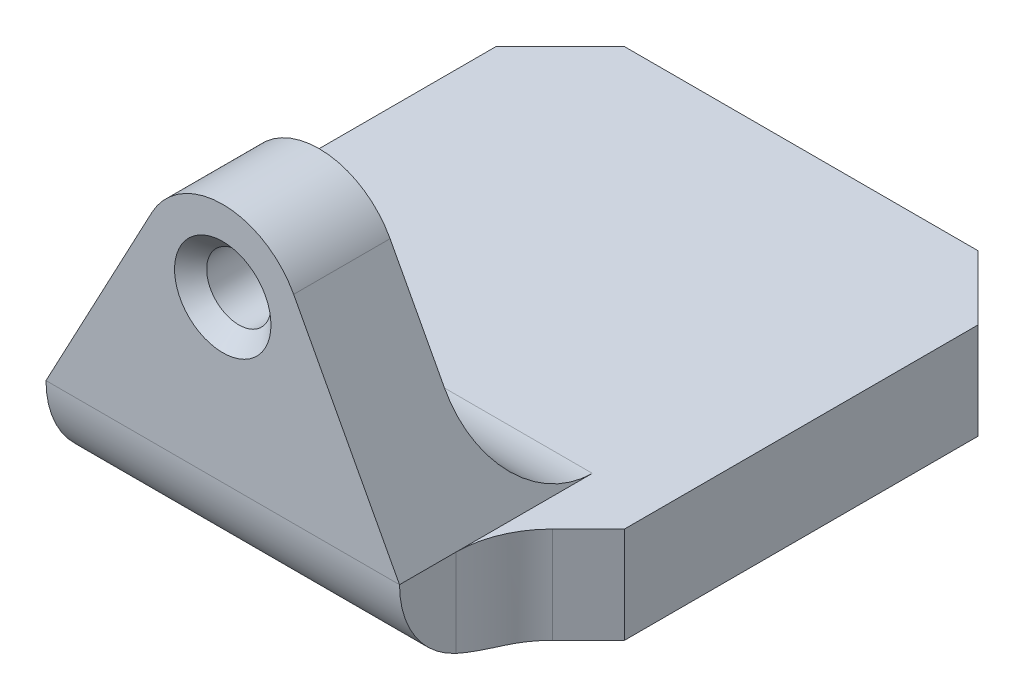
SolidWorks part; units mm, degrees
material "PE 高密度"
ref_plane "前视基准面" through (0, 0, 0) normal (0, 0, 1) x (1, 0, 0)
ref_plane "上视基准面" through (0, 0, 0) normal (0, 1, 0) x (1, 0, 0)
ref_plane "右视基准面" through (0, 0, 0) normal (1, 0, 0) x (0, 0, -1)
other "Configuration Table"
sketch "草图1" plane through (0, 0, 0) normal (0, 1, 0) x (1, 0, 0)
  line L1 (-15, 15) -> (15, 15)
  line L2 (-15, 15) -> (-15, -15)
  line L3 (-15, -15) -> (15, -15)
  line L4 (15, 15) -> (15, -15)
  line L5 (-15, 15) -> (15, -15) construction
  line L6 (-15, -15) -> (15, 15) construction
  point P0 (0, 0)
  dimension "D1" = 30
  dimension "D2" = 30
extrude "凸台-拉伸1" add sketch "草图1" along normal blind 6
chamfer "倒角1" distance 4 angle 45 4 edges at (-15, 3, -15) (15, 3, -15) (15, 3, 15) (-15, 3, 15)
sketch "草图2" plane through (0, 0, 15) normal (0, 0, 1) x (1, 0, 0)
  line L0 (0, 0) -> (0, 22.777) construction
  line L1 (-11, 6) -> (-4.4118, 18.3529)
  line L2 (11, 6) -> (4.4118, 18.3529)
  line L4 (-11, 0) -> (11, 0)
  line L5 (11, 0) -> (11, 6)
  line L6 (11, 6) -> (-11, 6)
  line L7 (-11, 6) -> (-11, 0)
  line L8 (-11, 0) -> (11, 0)
  line L9 (11, 0) -> (11, 6)
  line L11 (-11, 6) -> (-11, 0)
  circle A0 centre (0, 16) radius 2
  arc A1 (4.4118, 18.3529) -> (-4.4118, 18.3529) centre (0, 16) ccw
  dimension "D3" = 4
  dimension "D4" = 10
  dimension "D2" = 14
  dimension "D1" = 0
extrude "凸台-拉伸2" add sketch "草图2" along normal blind 6
fillet "圆角1" radius 6 1 edges at (0, 0, 21)
fillet "圆角2" radius 6 2 edges at (-11, 3, 15) (11, 3, 15)
fillet "圆角3" radius 6 1 edges at (0, 6, 15)
chamfer "倒角2" distance 1 angle 45 2 edges at (2, 16, 15) (2, 16, 21)
